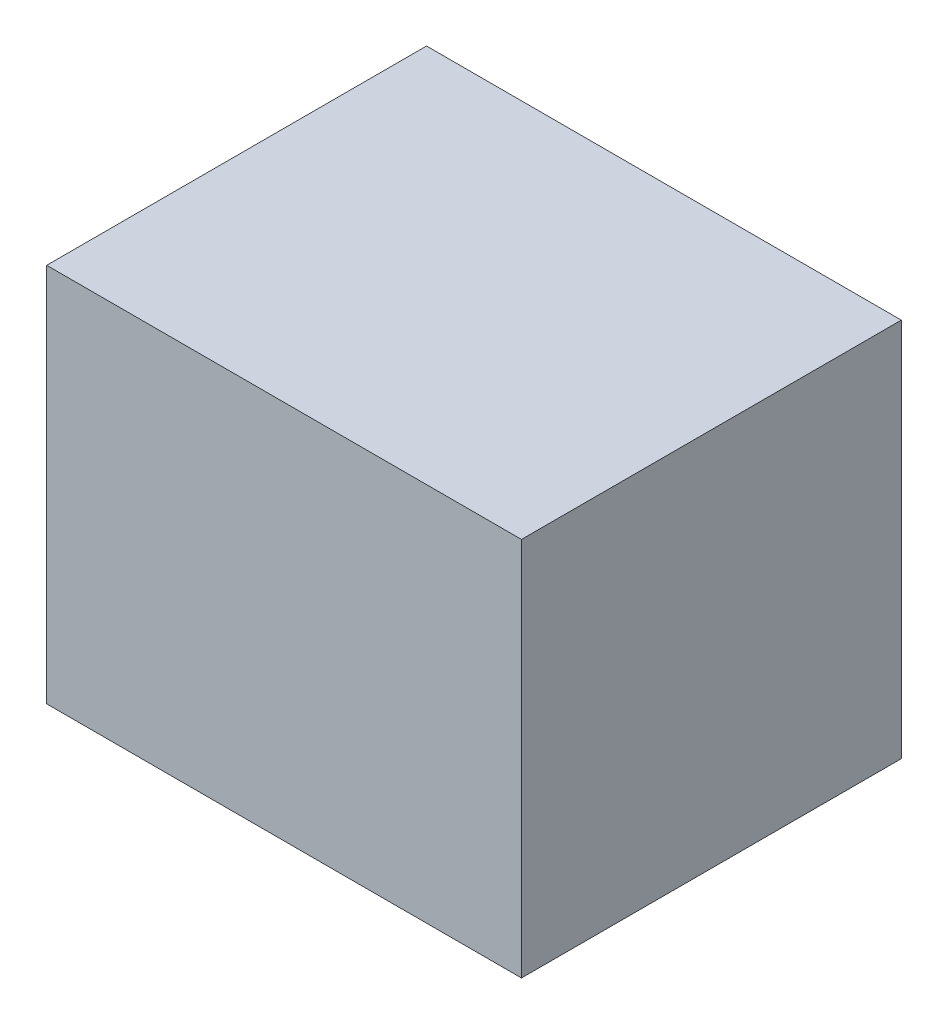
SolidWorks part; units mm, degrees
ref_plane "Płaszczyzna przednia" through (0, 0, 0) normal (0, 0, 1) x (1, 0, 0)
ref_plane "Płaszczyzna górna" through (0, 0, 0) normal (0, 1, 0) x (1, 0, 0)
ref_plane "Płaszczyzna prawa" through (0, 0, 0) normal (1, 0, 0) x (0, 0, -1)
sketch "Szkic1" plane through (0, 0, 0) normal (0, 0, 1) x (1, 0, 0)
  line L1 (-250, 30) -> (250, 30)
  line L2 (-250, 30) -> (-250, -30)
  line L3 (-250, -30) -> (250, -30)
  line L4 (250, 30) -> (250, -30)
  line L5 (-250, 30) -> (250, -30) construction
  line L6 (-250, -30) -> (250, 30) construction
  point P0 (0, 0)
  dimension "D1" = 500
  dimension "D2" = 60
extrude "Dodanie-wyciągnięcie1" add sketch "Szkic1" along normal blind 60
sketch "Szkic2" plane through (0, 0, 0) normal (0, 0, -1) x (-1, 0, 0)
  line L0 (0, 30) -> (0, -30) construction
  line L1 (-250, 30) -> (250, 30) construction
  line L2 (250, -30) -> (-250, -30) construction
  line L3 (-250, 0) -> (250, 0) construction
  line L4 (-250, -30) -> (-250, 30) construction
  line L5 (250, 30) -> (250, -30) construction
  line L6 (-250, 30) -> (0, 30) construction
  line L7 (0, 30) -> (250, 30) construction
  line L8 (-125, 30) -> (-125, -30) construction
  line L9 (125, 30) -> (125, -30) construction
  line L10 (-250, -30) -> (-125, -30) construction
  line L11 (-125, -30) -> (0, -30) construction
  line L12 (0, -30) -> (125, -30) construction
  line L13 (125, -30) -> (250, -30) construction
  line L14 (-187.5, -30) -> (-187.5, 30) construction
  line L15 (-62.5, -30) -> (-62.5, 30) construction
  line L16 (62.5, -30) -> (62.5, 30) construction
  line L17 (187.5, -30) -> (187.5, 30) construction
  circle A0 centre (-187.5, 0) radius 25
  circle A1 centre (-125, 0) radius 25
  circle A2 centre (-62.5, 0) radius 25
  circle A3 centre (0, 0) radius 25
  circle A4 centre (62.5, 0) radius 25
  circle A5 centre (125, 0) radius 25
  circle A6 centre (187.5, 0) radius 25
  dimension "D1" = 50
  dimension "D2" = 50
  dimension "D3" = 50
  dimension "D4" = 50
  dimension "D5" = 50
  dimension "D6" = 50
  dimension "D7" = 50
extrude "Wytnij-wyciągnięcie1" cut sketch "Szkic2" against normal blind 25
fillet "Zaokrąglenie2" radius 25 7 edges at (162.5, 0, 25) (-212.5, 0, 25) (-150, 0, 25) (-87.5, 0, 25) (-25, 0, 25) (37.5, 0, 25) (100, 0, 25)
sketch "Szkic5" plane through (250, 0, 0) normal (1, 0, 0) x (0, 0, -1)
  line L1 (-60, 30) -> (0, 30)
  line L2 (-60, 30) -> (-60, -30)
  line L3 (-60, -30) -> (0, -30)
  line L4 (0, 30) -> (0, -30)
extrude "Wytnij-wyciągnięcie2" cut sketch "Szkic5" against normal blind 400
sketch "Szkic6" plane through (-250, 0, 0) normal (-1, 0, 0) x (0, 0, 1)
  line L1 (0, 30) -> (60, 30)
  line L2 (0, 30) -> (0, -30)
  line L3 (0, -30) -> (60, -30)
  line L4 (60, 30) -> (60, -30)
extrude "Wytnij-wyciągnięcie4" cut sketch "Szkic6" against normal blind 25
